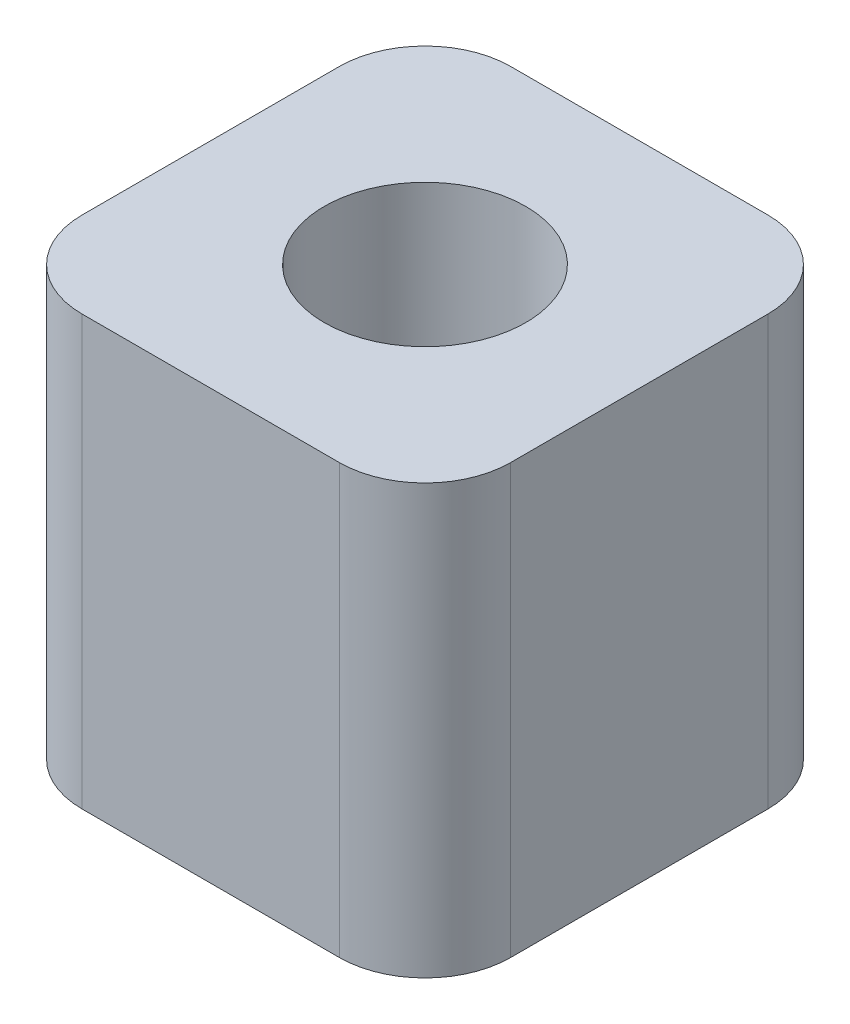
SolidWorks part; units mm, degrees
ref_plane "Front" through (0, 0, 0) normal (0, 0, 1) x (1, 0, 0)
ref_plane "Top" through (0, 0, 0) normal (0, 1, 0) x (1, 0, 0)
ref_plane "Right" through (0, 0, 0) normal (1, 0, 0) x (0, 0, -1)
sketch "Sketch1" plane through (0, 0, 0) normal (0, 1, 0) x (1, 0, 0)
  line L1 (-5, -5) -> (5, -5)
  line L2 (-5, -5) -> (-5, 5)
  line L3 (-5, 5) -> (5, 5)
  line L4 (5, -5) -> (5, 5)
  line L5 (-5, -5) -> (5, 5) construction
  line L6 (-5, 5) -> (5, -5) construction
  circle A0 centre (0, 0) radius 2.35
  point P0 (0, 0)
  dimension "D3" = 4.7
  dimension "D1" = 10
  dimension "D2" = 10
extrude "Boss-Extrude1" add sketch "Sketch1" along normal blind 10
fillet "Fillet1" radius 2 4 edges at (-5, 5, 5) (-5, 5, -5) (5, 5, -5) (5, 5, 5)
equation "\"D2@Sketch1\"=\"D1@Sketch1\""
